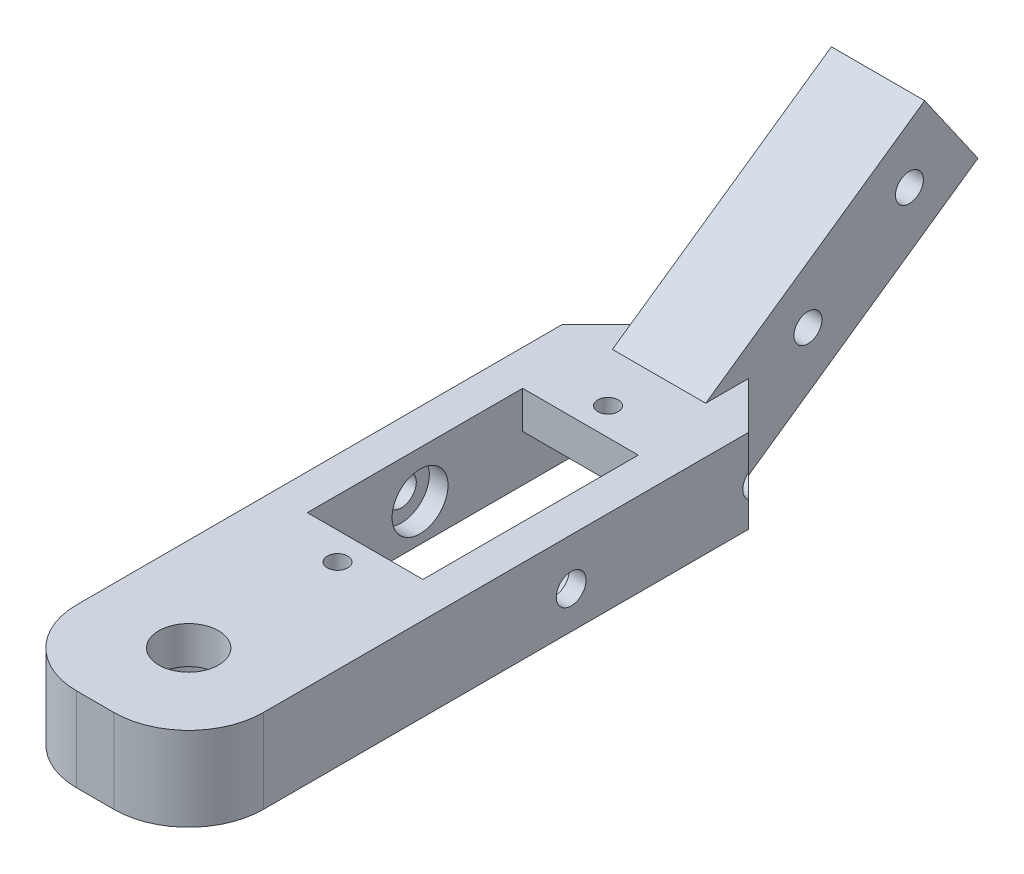
SolidWorks part; units mm, degrees
ref_plane "前视基准面" through (0, 0, 0) normal (0, 0, 1) x (1, 0, 0)
ref_plane "上视基准面" through (0, 0, 0) normal (0, 1, 0) x (1, 0, 0)
ref_plane "右视基准面" through (0, 0, 0) normal (1, 0, 0) x (0, 0, -1)
sketch "草图1" plane through (0, 0, 0) normal (1, 0, 0) x (0, 0, -1)
  line L1 (55, -4) -> (-10, -4)
  line L2 (55, -4) -> (55, 5)
  line L3 (55, 5) -> (-10, 5)
  line L4 (-10, -4) -> (-10, 5)
  line L5 (55, -4) -> (-10, 5) construction
  line L6 (55, 5) -> (-10, -4) construction
  point P0 (22.5, 0.5)
  point P5 (0, 0)
extrude "凸台-拉伸1" add sketch "草图1" along normal mid plane 20
sketch "草图2" plane through (0, -4, 0) normal (0, 1, 0) x (1, 0, 0)
  circle A0 centre (0, 0) radius 6.7
extrude "切除-拉伸1" cut sketch "草图2" along normal blind 5
sketch "草图4" plane through (0, 1, 0) normal (0, -1, 0) x (1, 0, 0)
  circle A0 centre (0, 0) radius 3.2
extrude "切除-拉伸3" cut sketch "草图4" against normal through all
sketch "草图3" plane through (0, 5, 0) normal (0, 1, 0) x (1, 0, 0)
  line L1 (6.2, 42) -> (-6.2, 42)
  line L2 (6.2, 42) -> (6.2, 18.9147)
  line L3 (6.2, 18.9147) -> (-6.2, 18.9147)
  line L4 (-6.2, 42) -> (-6.2, 18.9147)
  line L5 (6.2, 42) -> (-6.2, 18.9147) construction
  line L6 (6.2, 18.9147) -> (-6.2, 42) construction
  point P0 (0, 30.4574)
extrude "切除-拉伸2" cut sketch "草图3" against normal through all
sketch "草图5" plane through (0, -4, 0) normal (0, -1, 0) x (1, 0, 0)
  line L1 (6.2, -47.9147) -> (-6.2, -47.9147)
  line L2 (6.2, -47.9147) -> (6.2, -13)
  line L3 (6.2, -13) -> (-6.2, -13)
  line L4 (-6.2, -47.9147) -> (-6.2, -13)
  line L5 (6.2, -47.9147) -> (-6.2, -13) construction
  line L6 (6.2, -13) -> (-6.2, -47.9147) construction
  line L7 (-6.2, -42) -> (-6.2, -18.9147) construction
  line L8 (-6.2, -18.9147) -> (6.2, -18.9147) construction
  point P0 (0, -30.4574)
  point P7 (0, 0)
  point P8 (-6.2, -30.4574)
  point P11 (0, -18.9147)
extrude "切除-拉伸4" cut sketch "草图5" against normal offset from surface (5 mm away) 4 up to face at (0, 5, -30.4574)
sketch "草图6" plane through (0, 1, 0) normal (0, -1, 0) x (1, 0, 0)
  line L0 (-6.2, -30.4574) -> (6.2, -30.4574) construction
  line L1 (-6.2, -47.9147) -> (-6.2, -13) construction
  line L2 (6.2, -13) -> (6.2, -47.9147) construction
  line L3 (0, -30.4574) -> (0, -15.9574) construction
  circle A0 centre (0, -15.9574) radius 1.1
  circle A2 centre (0, -44.9574) radius 1.1
extrude "切除-拉伸5" cut sketch "草图6" against normal through all
fillet "圆角1" radius 8 2 edges at (-10, 0.5, 10) (10, 0.5, 10)
sketch "草图7" plane through (10, 0, 0) normal (1, 0, 0) x (0, 0, -1)
  line L0 (31.0016, 0) -> (51.0016, 0) construction
  circle A0 centre (51.0016, 0) radius 1.6
  circle A1 centre (31.0016, 0) radius 1.6
extrude "切除-拉伸6" cut sketch "草图7" against normal through all
sketch "草图8" plane through (-6.2, 0, 0) normal (1, 0, 0) x (0, 0, -1)
  circle A0 centre (31.0016, 0) radius 3
extrude "切除-拉伸7" cut sketch "草图8" against normal blind 2
mirror "镜向1" about plane through (0, 0, 0) normal (1, 0, 0) of "切除-拉伸7"
sketch "草图9" plane through (0, 0, 0) normal (1, 0, 0) x (0, 0, -1)
  line L0 (54.9927, -4.0051) -> (72.0635, 7.8882) construction
  line L1 (55, -4) -> (79.615, 13.1493)
  line L2 (79.615, 13.1493) -> (73.8986, 21.3544)
  line L3 (73.8986, 21.3544) -> (50.4246, 5)
  line L4 (55, 5) -> (-2, 5) construction
  line L5 (50.4246, 5) -> (55, 5)
  line L6 (55, 5) -> (55, -4)
  line L7 (76.7568, 17.2518) -> (55, 2.0938) construction
  circle A0 centre (72.2626, 14.1208) radius 1.5
  circle A1 centre (61.3838, 6.5414) radius 1.5
  point P1 (55, -4)
  point P6 (76.7568, 17.2518)
extrude "凸台-拉伸2" add sketch "草图9" along normal mid plane 10
chamfer "倒角1" distance 5 angle 45 2 edges at (-10, 0.5, -55) (10, 0.5, -55)
